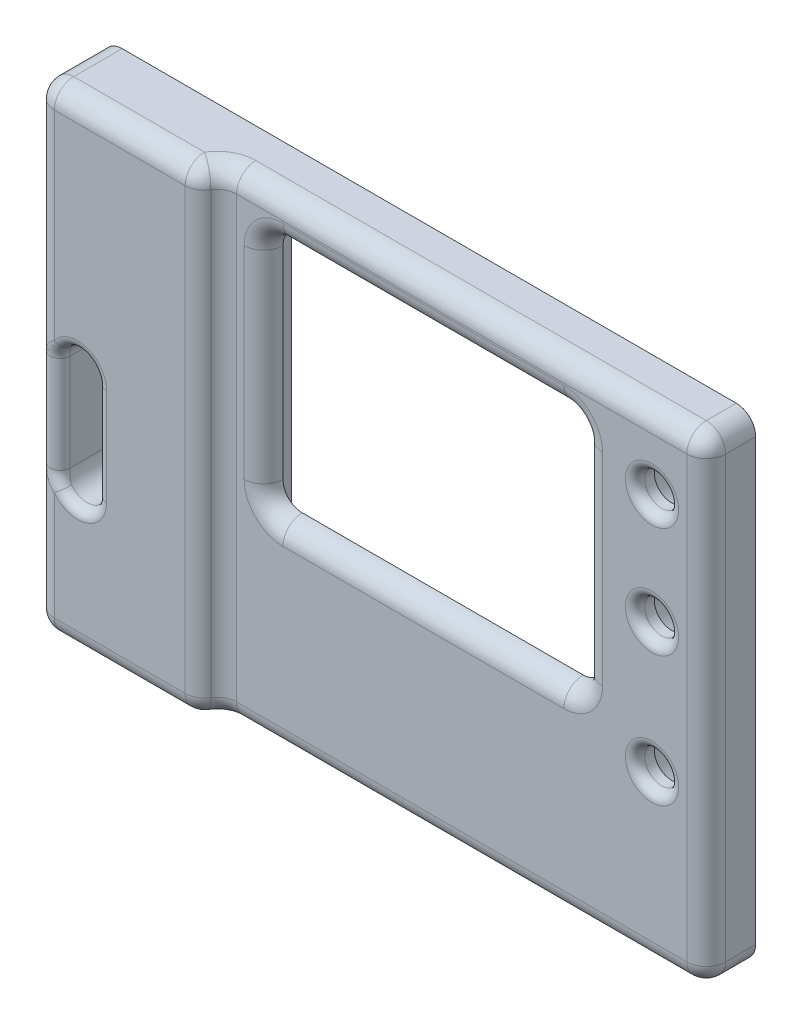
SolidWorks part; units mm, degrees
ref_plane "Front" through (0, 0, 0) normal (0, 0, 1) x (1, 0, 0)
ref_plane "Top" through (0, 0, 0) normal (0, 1, 0) x (1, 0, 0)
ref_plane "Right" through (0, 0, 0) normal (1, 0, 0) x (0, 0, -1)
sketch "Brd" plane through (0, 0, 0) normal (0, 0, 1) x (1, 0, 0)
  line L0 (-31.5, 0) -> (31.5, 0) construction
  line L1 (-31.5, -22.5) -> (31.5, -22.5)
  line L2 (-31.5, -22.5) -> (-31.5, 22.5)
  line L3 (-31.5, 22.5) -> (31.5, 22.5)
  line L4 (31.5, -22.5) -> (31.5, 22.5)
  line L5 (-31.5, -22.5) -> (31.5, 22.5) construction
  line L6 (-31.5, 22.5) -> (31.5, -22.5) construction
  line L7 (-31.3, 0.3) -> (-27.3, 0.3)
  line L8 (-31.3, 0.3) -> (-31.3, -9.7)
  line L9 (-31.3, -9.7) -> (-27.3, -9.7)
  line L10 (-27.3, 0.3) -> (-27.3, -9.7)
  line L11 (-31.3, 0.3) -> (-27.3, -9.7) construction
  line L12 (-31.3, -9.7) -> (-27.3, 0.3) construction
  line L13 (-26.7, 6.9) -> (-21.1, 6.9)
  line L14 (-26.7, 6.9) -> (-26.7, -9.1)
  line L15 (-26.7, -9.1) -> (-21.1, -9.1)
  line L16 (-21.1, 6.9) -> (-21.1, -9.1)
  line L17 (0, 22.5) -> (0, -22.5) construction
  line L18 (25.1, 8.9) -> (31.1, 8.9)
  line L19 (-14.2, 22.5) -> (23.2, 22.5)
  line L20 (-14.2, 22.5) -> (-14.2, -14.4)
  line L21 (-14.2, -14.4) -> (23.2, -14.4)
  line L22 (23.2, 22.5) -> (23.2, -14.4)
  line L23 (-6.2, -14.4) -> (0, -14.4)
  line L24 (-6.2, -14.4) -> (-6.2, -22.5)
  line L25 (-6.2, -22.5) -> (0, -22.5)
  line L26 (0, -14.4) -> (0, -22.5)
  line L27 (25.1, 20.3) -> (31.1, 20.3)
  line L28 (25.1, 20.3) -> (25.1, 14.3)
  line L29 (25.1, 14.3) -> (31.1, 14.3)
  line L30 (31.1, 20.3) -> (31.1, 14.3)
  line L31 (25.1, 20.3) -> (31.1, 14.3) construction
  line L32 (25.1, 14.3) -> (31.1, 20.3) construction
  line L33 (25.1, 8.9) -> (25.1, 2.9)
  line L34 (25.1, 2.9) -> (31.1, 2.9)
  line L35 (31.1, 8.9) -> (31.1, 2.9)
  line L36 (25.1, 8.9) -> (31.1, 2.9) construction
  line L37 (25.1, 2.9) -> (31.1, 8.9) construction
  line L38 (25.1, -4.5) -> (31.1, -4.5)
  line L39 (25.1, -4.5) -> (25.1, -10.5)
  line L40 (25.1, -10.5) -> (31.1, -10.5)
  line L41 (31.1, -4.5) -> (31.1, -10.5)
  line L42 (25.1, -4.5) -> (31.1, -10.5) construction
  line L43 (25.1, -10.5) -> (31.1, -4.5) construction
  line L44 (28.1, 17.3) -> (28.1, -17.9611) construction
  line L45 (-29.04, -21.5729) -> (-29.04, -22.5)
  line L46 (4.4, -15.8) -> (13.7, -15.8)
  line L47 (4.4, -15.8) -> (4.4, -18)
  line L48 (4.4, -18) -> (13.7, -18)
  line L49 (13.7, -15.8) -> (13.7, -18)
  line L50 (-12, 20.5) -> (21, 20.5)
  line L51 (-12, 20.5) -> (-12, -4.4)
  line L52 (-12, -4.4) -> (21, -4.4)
  line L53 (21, 20.5) -> (21, -4.4)
  line L54 (-23.96, -21.5729) -> (-23.96, -22.5)
  line L55 (-26.5, -17.5) -> (-26.5, -22.5) construction
  line L56 (-29.04, -21.5729) -> (-23.96, -21.5729) construction
  line L58 (-20.7, -17.5) -> (-13.1, -17.5)
  line L59 (-20.7, -17.5) -> (-20.7, -22.5)
  line L60 (-20.7, -22.5) -> (-13.1, -22.5)
  line L61 (-13.1, -17.5) -> (-13.1, -22.5)
  circle A0 centre (-26.5, -17.5) radius 4.8
  point P0 (0, 0)
  point P8 (-29.3, -4.7)
  point P29 (28.1, 17.3)
  point P34 (28.1, 5.9)
  point P39 (28.1, -7.5)
  dimension "D5" = 9.6
  dimension "D3" = 26.5
  dimension "D4" = 17.5
  dimension "D1" = 45
  dimension "D2" = 63
  dimension "D6" = 4.7
  dimension "D7" = 29.3
  dimension "D8" = 4
  dimension "D9" = 10
  dimension "D10" = 6.9
  dimension "D11" = 9.1
  dimension "D12" = 21.1
  dimension "D13" = 26.7
  dimension "D14" = 14.2
  dimension "D15" = 23.2
  dimension "D16" = 14.4
  dimension "D17" = 6.2
  dimension "D18" = 6
  dimension "D19" = 6
  dimension "D20" = 6
  dimension "D21" = 28.1
  dimension "D22" = 17.3
  dimension "D23" = 5.9
  dimension "D24" = 7.5
  dimension "D25" = 15.8
  dimension "D26" = 2.2
  dimension "D27" = 9.3
  dimension "D28" = 4.4
  dimension "D29" = 2
  dimension "D30" = 2.2
  dimension "D31" = 2.2
  dimension "D32" = 10
  dimension "D33" = 5.08
  dimension "D34" = 7.6
  dimension "D35" = 10.8
  dimension "D36" = 5
sketch "Sketch2" plane through (0, 0, 0) normal (0, 0, 1) x (1, 0, 0)
  line L0 (31.5, -22.5) -> (31.5, 22.5) construction
  line L1 (-33.7, 24.7) -> (33.7, 24.7)
  line L2 (-33.7, 24.7) -> (-33.7, -24.7)
  line L3 (-33.7, -24.7) -> (33.7, -24.7)
  line L4 (33.7, 24.7) -> (33.7, -24.7)
  line L5 (-33.7, 24.7) -> (33.7, -24.7) construction
  line L6 (-33.7, -24.7) -> (33.7, 24.7) construction
  line L7 (-31.5, 22.5) -> (31.5, 22.5) construction
  point P0 (0, 0)
  dimension "D1" = 2.2
  dimension "D2" = 2.2
extrude "Main block" add sketch "Sketch2" along normal blind 7
sketch "Sketch3" plane through (0, 0, 7) normal (0, 0, 1) x (1, 0, 0)
  line L1 (-12, 20.5) -> (21, 20.5)
  line L2 (-12, 20.5) -> (-12, -4.4)
  line L3 (-12, -4.4) -> (21, -4.4)
  line L4 (21, 20.5) -> (21, -4.4)
extrude "LCD through cut" cut sketch "Sketch3" against normal through all
sketch "Sketch4" plane through (0, 0, 0) normal (0, 0, -1) x (-1, 0, 0)
  line L0 (-23.2, 22.5) -> (14.2, 22.5)
  line L2 (14.2, -14.4) -> (6.2, -14.4)
  line L3 (0, -14.4) -> (0, -19.3)
  line L4 (6.2, -22.5) -> (0, -22.5)
  line L5 (6.2, -14.4) -> (6.2, -19.3)
  line L6 (0, -14.4) -> (-23.2, -14.4)
  line L7 (14.2, 19.3) -> (14.2, -11.2)
  line L10 (31.5, 22.5) -> (-31.5, 22.5) construction
  line L11 (14.2, 22.5) -> (14.2, -14.4) construction
  line L12 (-23.2, 19.3) -> (-23.2, -11.2)
  line L13 (-23.2, 22.5) -> (-23.2, -14.4) construction
  line L15 (0, -14.4) -> (0, -22.5) construction
  line L16 (6.2, -14.4) -> (6.2, -22.5) construction
  arc A0 (14.2, 22.5) -> (14.2, 19.3) centre (14.2, 20.9) cw
  arc A1 (14.2, -11.2) -> (14.2, -14.4) centre (14.2, -12.8) cw
  arc A2 (-23.2, 19.3) -> (-23.2, 22.5) centre (-23.2, 20.9) cw
  arc A3 (-23.2, -14.4) -> (-23.2, -11.2) centre (-23.2, -12.8) cw
  arc A4 (0, -22.5) -> (0, -19.3) centre (0, -20.9) cw
  arc A5 (6.2, -19.3) -> (6.2, -22.5) centre (6.2, -20.9) cw
  dimension "D1" = 1.6
  dimension "D2" = 1.6
  dimension "D3" = 1.6
  dimension "D4" = 1.6
  dimension "D5" = 1.6
  dimension "D6" = 1.6
extrude "LCD cut" cut sketch "Sketch4" against normal blind 3.1
sketch "Sketch5" plane through (0, 0, 0) normal (0, 0, -1) x (-1, 0, 0)
  line L0 (-13.7, -16.9) -> (-4.4, -16.9) construction
  line L1 (-13.7, -15.25) -> (-4.4, -15.25)
  line L2 (-13.7, -18.55) -> (-4.4, -18.55)
  line L3 (-4.4, -15.8) -> (-4.4, -18) construction
  line L4 (-13.7, -15.8) -> (-13.7, -18) construction
  arc A0 (-13.7, -15.25) -> (-13.7, -18.55) centre (-13.7, -16.9) ccw
  arc A1 (-4.4, -18.55) -> (-4.4, -15.25) centre (-4.4, -16.9) ccw
  point P2 (-9.05, -16.9)
  dimension "D1" = 3.3
extrude "quartz cut" cut sketch "Sketch5" against normal blind 3.1
sketch "Sketch6" plane through (0, 0, 0) normal (0, 0, -1) x (-1, 0, 0)
  line L0 (-31.5, -22.5) -> (-31.5, 22.5) construction
  line L1 (-28.2, 12.5748) -> (-28, 12.5748)
  line L2 (-31.5, 15.8748) -> (-31.5, 18.7252)
  line L3 (-28.2, 22.0252) -> (-28, 22.0252)
  line L4 (-24.7, 15.8748) -> (-24.7, 18.7252)
  line L6 (-28.2, 1.1748) -> (-28, 1.1748)
  line L7 (-31.5, 4.4748) -> (-31.5, 7.3252)
  line L8 (-28.2, 10.6252) -> (-28, 10.6252)
  line L9 (-28, -12.2252) -> (-28.2, -12.2252)
  line L10 (-24.7, -8.9252) -> (-24.7, -6.0748)
  line L11 (-28, -2.7748) -> (-28.2, -2.7748)
  line L12 (-31.5, -8.9252) -> (-31.5, -6.0748)
  line L13 (-31.5, 12.5748) -> (-24.7, 22.0252) construction
  line L14 (-31.5, 22.0252) -> (-24.7, 12.5748) construction
  line L15 (-24.7, 4.4748) -> (-24.7, 7.3252)
  line L16 (-31.5, 1.1748) -> (-24.7, 10.6252) construction
  line L17 (-31.5, 10.6252) -> (-24.7, 1.1748) construction
  line L18 (-24.7, -12.2252) -> (-31.5, -2.7748) construction
  line L19 (-24.7, -2.7748) -> (-31.5, -12.2252) construction
  arc A0 (-28.2, 12.5748) -> (-31.5, 15.8748) centre (-28.2, 15.8748) cw
  arc A1 (-28, 12.5748) -> (-24.7, 15.8748) centre (-28, 15.8748) ccw
  arc A2 (-28, 22.0252) -> (-24.7, 18.7252) centre (-28, 18.7252) cw
  arc A3 (-31.5, 18.7252) -> (-28.2, 22.0252) centre (-28.2, 18.7252) cw
  arc A4 (-28.2, 1.1748) -> (-31.5, 4.4748) centre (-28.2, 4.4748) cw
  arc A5 (-28, 1.1748) -> (-24.7, 4.4748) centre (-28, 4.4748) ccw
  arc A6 (-28, 10.6252) -> (-24.7, 7.3252) centre (-28, 7.3252) cw
  arc A7 (-31.5, 7.3252) -> (-28.2, 10.6252) centre (-28.2, 7.3252) cw
  arc A8 (-28.2, -12.2252) -> (-31.5, -8.9252) centre (-28.2, -8.9252) cw
  arc A9 (-28, -12.2252) -> (-24.7, -8.9252) centre (-28, -8.9252) ccw
  arc A10 (-24.7, -6.0748) -> (-28, -2.7748) centre (-28, -6.0748) ccw
  arc A11 (-28.2, -2.7748) -> (-31.5, -6.0748) centre (-28.2, -6.0748) ccw
  point P0 (-28.1, 17.3)
  point P6 (-28.1, 5.9)
  point P12 (-28.1, -7.5)
  dimension "D1" = 3.3
  dimension "D2" = 3.3
  dimension "D3" = 3.3
extrude "Btns cut" cut sketch "Sketch6" against normal blind 3.1
sketch "Sketch7" plane through (0, 0, 7) normal (0, 0, 1) x (1, 0, 0)
  circle A0 centre (28.1, 17.3) radius 1.75
  circle A1 centre (28.1, 5.9) radius 1.75
  circle A2 centre (28.1, -7.5) radius 1.75
  dimension "D1" = 3.5
extrude "Btns through cut" cut sketch "Sketch7" against normal through all
sketch "Sketch8" plane through (0, 0, 0) normal (0, 0, -1) x (-1, 0, 0)
  line L0 (27.3, 0.3) -> (27.3, -9.7)
  line L1 (31.3, -9.7) -> (31.3, 0.3)
  arc A0 (27.3, 0.3) -> (31.3, 0.3) centre (29.3, 0.3) cw
  arc A1 (31.3, -9.7) -> (27.3, -9.7) centre (29.3, -9.7) cw
extrude "Conn through cut" cut sketch "Sketch8" against normal through all
sketch "Sketch9" plane through (0, 0, 0) normal (0, 0, -1) x (-1, 0, 0)
  line L0 (21.1, 6.9) -> (21.1, -9.1) construction
  line L2 (21.1, 6.9) -> (21.1, -9.1)
  line L4 (26.7, 6.9) -> (26.7, -9.1)
  line L5 (26.7, 6.9) -> (26.7, -9.1) construction
  arc A0 (21.1, 6.9) -> (26.7, 6.9) centre (23.9, 6.9) cw
  arc A1 (26.7, -9.1) -> (21.1, -9.1) centre (23.9, -9.1) cw
extrude "Motor cut" cut sketch "Sketch9" against normal blind 6.2
sketch "Sketch11" plane through (0, 0, 0) normal (0, 0, -1) x (-1, 0, 0)
  line L0 (23.96, -24.7) -> (23.96, -21.5729)
  line L1 (33.7, -24.7) -> (-33.7, -24.7) construction
  line L2 (29.04, -21.5729) -> (29.04, -24.7)
  line L3 (29.04, -24.7) -> (23.96, -24.7)
  line L5 (21.7, -18.441) -> (21.7, -16)
  line L6 (25, -12.7) -> (28, -12.7)
  line L7 (31.3, -16) -> (31.3, -18.441)
  circle A0 centre (26.5, -17.5) radius 4.8 construction
  arc A1 (28, -12.7) -> (31.3, -16) centre (28, -16) cw
  arc A2 (21.7, -16) -> (25, -12.7) centre (25, -16) cw
  arc A3 (23.96, -21.5729) -> (21.7, -18.441) centre (25, -18.441) cw
  arc A4 (31.3, -18.441) -> (29.04, -21.5729) centre (28, -18.441) cw
  dimension "D1" = 3.3
  dimension "D2" = 3.3
  dimension "D3" = 3.3
extrude "Buzzer cut" cut sketch "Sketch11" against normal blind 5.2
sketch "Sketch12" plane through (0, 0, 7) normal (0, 0, 1) x (1, 0, 0)
  line L0 (-33.7, -24.7) -> (33.7, -24.7) construction
  line L1 (33.7, 24.7) -> (-16.2, 24.7)
  line L2 (33.7, 24.7) -> (33.7, -24.7)
  line L3 (33.7, -24.7) -> (-16.2, -24.7)
  line L4 (-16.2, 24.7) -> (-16.2, -24.7)
  line L5 (-14.2, 22.5) -> (-14.2, -14.4) construction
  dimension "D1" = 2
extrude "Cut-Extrude9" cut sketch "Sketch12" against normal offset from surface (1.9 mm away) 2 up to face at (1.2429, -5.7143, 3.1)
fillet "Fillet1" radius 2 1 edges at (-16.2, 0, 7)
fillet "Fillet2" radius 2 1 edges at (-16.2, 0, 5.1)
fillet "Fillet3" radius 2 14 edges at (9.4535, -24.7, 5.1) (-15.7678, -24.7, 5.3536) (-17.2228, -24.7, 6.7464) (9.4535, 24.7, 5.1) (-15.7678, 24.7, 5.3536) (-17.2228, 24.7, 6.7464) (33.7, -24.7, 2.55) (-25.9487, -24.7, 7) (-33.7, -24.7, 3.5) (-33.7, 24.7, 3.5) (-33.7, 0, 7) (33.7, 24.7, 2.55) (33.7, 0, 5.1) (-25.9487, 24.7, 7)
fillet "Fillet4" radius 2 4 edges at (4.5, -4.4, 5.1) (-12, 8.05, 5.1) (21, 8.05, 5.1) (4.5, 20.5, 5.1)
fillet "Fillet6" radius 1 3 edges at (29.85, -7.5, 5.1) (29.85, 5.9, 5.1) (29.85, 17.3, 5.1)
fillet "Fillet7" radius 1 4 edges at (-29.3, 2.3, 7) (-31.3, -4.7, 7) (-29.3, -11.7, 7) (-27.3, -4.7, 7)
sketch "Sketch13" plane through (0, 0, 0) normal (0, 0, -1) x (-1, 0, 0)
  line L0 (23.96, -24.7) -> (-31.7, -24.7) construction
  line L1 (13.1, -24.7) -> (20.7, -24.7)
  line L2 (13.1, -24.7) -> (13.1, -18.1)
  line L3 (16.4, -14.8) -> (17.4, -14.8)
  line L4 (20.7, -24.7) -> (20.7, -18.1)
  line L5 (13.1, -17.5) -> (13.1, -22.5) construction
  line L6 (20.7, -17.5) -> (20.7, -22.5) construction
  arc A0 (17.4, -14.8) -> (20.7, -18.1) centre (17.4, -18.1) cw
  arc A1 (13.1, -18.1) -> (16.4, -14.8) centre (16.4, -18.1) cw
  dimension "D1" = 3.3
  dimension "D2" = 9.9
extrude "Cut-Extrude10" cut sketch "Sketch13" against normal blind 3
